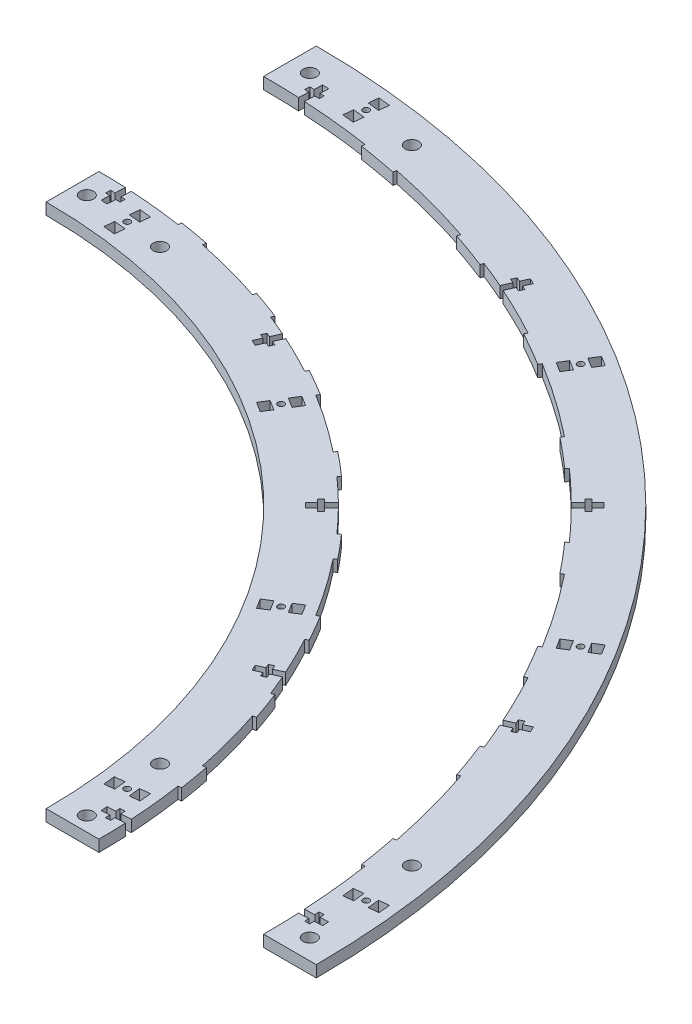
SolidWorks part; units mm, degrees
material "Custom Plastic"
ref_plane "Front Plane" through (0, 0, 0) normal (0, 0, 1) x (1, 0, 0)
ref_plane "Top Plane" through (0, 0, 0) normal (0, 1, 0) x (1, 0, 0)
ref_plane "Right Plane" through (0, 0, 0) normal (1, 0, 0) x (0, 0, -1)
sketch "Sketch1" plane through (0, 0, 0) normal (0, 1, 0) x (1, 0, 0)
  line L0 (280.2099, 0) -> (318.3099, 0)
  line L1 (318.3099, 0) -> (356.4099, 0)
  circle A0 centre (0, 0) radius 318.3099
  circle A1 centre (0, 0) radius 280.2099
  circle A2 centre (0, 0) radius 356.4099
  dimension "D1" = 636.6198
  dimension "D2" = 76.2
sketch "Sketch2" plane through (0, 0, 0) normal (0, 1, 0) x (1, 0, 0)
  line L0 (356.4099, 0) -> (383.3974, 0) construction
  line L1 (280.2099, 0) -> (253.2224, 0) construction
  line L2 (0, 0) -> (0, 470.2302) construction
  line L3 (0, 383.3974) -> (0, 253.2224)
  line L4 (383.3974, 0) -> (253.2224, 0)
  arc A0 (253.2224, 0) -> (0, 253.2224) centre (0, 0) ccw
  arc A1 (383.3974, 0) -> (0, 383.3974) centre (0, 0) ccw
  circle A3 centre (0, 0) radius 253.2224 construction
  circle A4 centre (0, 0) radius 383.3974 construction
  dimension "D1" = 26.9875
  dimension "D2" = 90
extrude "Boss-Extrude1" add sketch "Sketch2" along normal blind 5.588
sketch "Sketch6" plane through (0, 0, 0) normal (0, 1, 0) x (1, 0, 0)
  line L1 (318.3099, -318.3099) -> (-318.3099, -318.3099)
  line L2 (318.3099, -318.3099) -> (318.3099, 318.3099)
  line L3 (318.3099, 318.3099) -> (-318.3099, 318.3099)
  line L4 (-318.3099, -318.3099) -> (-318.3099, 318.3099)
  line L5 (318.3099, -318.3099) -> (-318.3099, 318.3099) construction
  line L6 (318.3099, 318.3099) -> (-318.3099, -318.3099) construction
  circle A0 centre (0, 0) radius 318.3099 construction
  point P0 (0, 0)
sketch "Sketch3" plane through (0, 0, 0) normal (0, 1, 0) x (1, 0, 0)
  line L0 (0, 0) -> (394.3747, 10.3271) construction
  line L1 (318.3099, 0) -> (356.4099, 0) construction
  line L2 (277.132, 41.4177) -> (275.562, 41.183)
  line L3 (0, 0) -> (390.1765, 58.3123) construction
  line L7 (354.0651, 52.9154) -> (352.495, 52.6807)
  line L8 (357.8747, 9.3713) -> (356.2878, 9.3297)
  line L10 (280.1139, 7.335) -> (278.5269, 7.2935)
  arc A1 (356.2878, 9.3297) -> (352.495, 52.6807) centre (0, 0) ccw
  circle A2 centre (0, 0) radius 356.4099 construction
  arc A4 (357.8747, 9.3713) -> (354.0651, 52.9154) centre (0, 0) ccw
  arc A6 (278.5269, 7.2935) -> (275.562, 41.183) centre (0, 0) ccw
  arc A7 (280.1139, 7.335) -> (277.132, 41.4177) centre (0, 0) ccw
  circle A8 centre (0, 0) radius 280.2099 construction
  dimension "D1" = 1.5
  dimension "D2" = 7
  dimension "D4" = 1.5875
extrude "Cut-Extrude2" cut sketch "Sketch3" along normal through all
sketch "Rotation Axis" plane through (0, 0, 0) normal (0, 0, 1) x (1, 0, 0)
  line L0 (0, 0) -> (0, 52.4129)
pattern_circular "CirPattern1" count 36 over 360 about axis through (0, 0, 0) along (0, 1, 0) of "Cut-Extrude2"
sketch "Sketch8" plane through (0, 0, 0) normal (0, 1, 0) x (1, 0, 0)
  line L0 (0, 0) -> (216.6823, 22.7742) construction
  line L1 (253.2224, 0) -> (383.3974, 0) construction
  line L2 (256.8637, 24.1881) -> (261.6001, 24.6859)
  line L3 (256.8637, 24.1881) -> (256.2796, 29.7455)
  line L4 (261.6001, 24.6859) -> (261.016, 30.2433)
  line L5 (256.2796, 29.7455) -> (261.016, 30.2433)
  line L6 (256.8637, 24.1881) -> (261.016, 30.2433) construction
  line L7 (261.6001, 24.6859) -> (256.2796, 29.7455) construction
  line L8 (361.0647, 35.14) -> (365.8011, 35.6379)
  line L9 (361.0647, 35.14) -> (360.4806, 40.6974)
  line L10 (365.8011, 35.6379) -> (365.217, 41.1952)
  line L11 (360.4806, 40.6974) -> (365.217, 41.1952)
  line L12 (361.0647, 35.14) -> (365.217, 41.1952) construction
  line L13 (365.8011, 35.6379) -> (360.4806, 40.6974) construction
  line L14 (267.9153, 25.3496) -> (272.6517, 25.8475)
  line L15 (267.9153, 25.3496) -> (267.3312, 30.907)
  line L16 (272.6517, 25.8475) -> (272.0676, 31.4048)
  line L17 (267.3312, 30.907) -> (272.0676, 31.4048)
  line L18 (267.9153, 25.3496) -> (272.0676, 31.4048) construction
  line L19 (272.6517, 25.8475) -> (267.3312, 30.907) construction
  line L20 (372.1163, 36.3016) -> (376.8527, 36.7994)
  line L21 (372.1163, 36.3016) -> (371.5322, 41.859)
  line L22 (376.8527, 36.7994) -> (376.2686, 42.3568)
  line L23 (371.5322, 41.859) -> (376.2686, 42.3568)
  line L24 (372.1163, 36.3016) -> (376.2686, 42.3568) construction
  line L25 (376.8527, 36.7994) -> (371.5322, 41.859) construction
  line L26 (261.308, 27.4646) -> (267.6232, 28.1283) construction
  line L27 (365.5091, 38.4166) -> (371.8243, 39.0803) construction
  circle A0 centre (264.4656, 27.7965) radius 1.524
  circle A1 centre (368.6667, 38.7484) radius 1.524
  arc A2 (383.3974, 0) -> (0, 383.3974) centre (0, 0) ccw construction
  arc A3 (253.2224, 0) -> (0, 253.2224) centre (0, 0) ccw construction
  point P5 (269.9914, 28.3772)
  point P6 (258.9398, 27.2157)
  point P7 (363.1409, 38.1676)
  point P13 (374.1925, 39.3292)
  point P29 (251.8352, 26.4689)
  point P30 (381.2971, 40.0759)
  dimension "D7" = 3.048
  dimension "D1" = 6
  dimension "D2" = 4.7625
  dimension "D3" = 5.588
  dimension "D4" = 6.35
  dimension "D5" = 4.7625
  dimension "D6" = 4.7625
extrude "Cut-Extrude3" cut sketch "Sketch8" along normal through all
pattern_circular "CirPattern3" count 4 every 26 about axis through (0, 0, 0) along (0, 1, 0) of "Cut-Extrude3"
sketch "Sketch11" plane through (0, 0, 0) normal (0, 1, 0) x (1, 0, 0)
  circle A0 centre (0, 0) radius 356.4099
  circle A1 centre (0, 0) radius 356.4099 construction
  circle A2 centre (0, 0) radius 280.2099
  circle A3 centre (0, 0) radius 280.2099 construction
extrude "Cut-Extrude7" cut sketch "Sketch11" along normal through all
sketch "Sketch12" plane through (0, 0, 0) normal (0, 1, 0) x (1, 0, 0)
  line L0 (0, 0) -> (536.846, 28.1349) construction
  line L1 (362.4514, 15.3241) -> (364.8293, 15.4487)
  line L2 (362.4514, 15.3241) -> (362.0676, 22.6464) construction
  line L3 (364.8293, 15.4487) -> (364.4456, 22.771) construction
  line L4 (362.0676, 22.6464) -> (364.4456, 22.771)
  line L5 (362.4514, 15.3241) -> (364.4456, 22.771) construction
  line L6 (364.8293, 15.4487) -> (362.0676, 22.6464) construction
  line L7 (355.9979, 17.131) -> (368.6805, 17.7956) construction
  line L8 (355.9979, 17.131) -> (355.8384, 20.1748)
  line L9 (368.6805, 17.7956) -> (368.521, 20.8395)
  line L10 (355.8384, 20.1748) -> (368.521, 20.8395) construction
  line L11 (355.9979, 17.131) -> (368.521, 20.8395) construction
  line L12 (368.6805, 17.7956) -> (355.8384, 20.1748) construction
  line L13 (271.2943, 10.5467) -> (273.6723, 10.6714)
  line L14 (271.2943, 10.5467) -> (270.9106, 17.869) construction
  line L15 (273.6723, 10.6714) -> (273.2886, 17.9937) construction
  line L16 (270.9106, 17.869) -> (273.2886, 17.9937)
  line L17 (271.2943, 10.5467) -> (273.2886, 17.9937) construction
  line L18 (273.6723, 10.6714) -> (270.9106, 17.869) construction
  line L19 (267.2189, 12.4783) -> (279.9015, 13.1429) construction
  line L20 (267.2189, 12.4783) -> (267.0594, 15.5221)
  line L21 (279.9015, 13.1429) -> (279.742, 16.1867)
  line L22 (267.0594, 15.5221) -> (279.742, 16.1867) construction
  line L23 (267.2189, 12.4783) -> (279.742, 16.1867) construction
  line L24 (279.9015, 13.1429) -> (267.0594, 15.5221) construction
  line L25 (280.2099, 0) -> (318.3099, 0) construction
  line L26 (267.0594, 15.5221) -> (271.0227, 15.7298)
  line L27 (271.0227, 15.7298) -> (270.9106, 17.869)
  line L28 (273.2886, 17.9937) -> (273.4007, 15.8544)
  line L29 (273.4007, 15.8544) -> (279.742, 16.1867)
  line L30 (273.6723, 10.6714) -> (273.5602, 12.8106)
  line L31 (273.5602, 12.8106) -> (279.9015, 13.1429)
  line L32 (271.2943, 10.5467) -> (271.1822, 12.686)
  line L33 (271.1822, 12.686) -> (267.2189, 12.4783)
  line L34 (362.0676, 22.6464) -> (362.1797, 20.5071)
  line L35 (362.1797, 20.5071) -> (355.8384, 20.1748)
  line L36 (364.4456, 22.771) -> (364.5577, 20.6318)
  line L37 (364.5577, 20.6318) -> (368.521, 20.8395)
  line L38 (368.6805, 17.7956) -> (364.7172, 17.5879)
  line L39 (364.7172, 17.5879) -> (364.8293, 15.4487)
  line L40 (362.4514, 15.3241) -> (362.3392, 17.4633)
  line L41 (362.3392, 17.4633) -> (355.9979, 17.131)
  line L58 (15.4071, 364.0367) -> (22.7294, 363.6529) construction
  circle A2 centre (0, 0) radius 280.2099 construction
  circle A3 centre (0, 0) radius 356.4099 construction
  point P4 (363.4485, 19.0475)
  point P5 (273.4804, 14.3325)
  point P6 (362.2595, 18.9852)
  point P12 (355.9182, 18.6529)
  point P18 (272.2914, 14.2702)
  dimension "D1" = 2.3813
  dimension "D2" = 7.3323
  dimension "D3" = 3.048
  dimension "D4" = 12.7
  dimension "D5" = 6.35
  dimension "D6" = 6.35
  dimension "D7" = 3
extrude "Cut-Extrude16" cut sketch "Sketch12" along normal blind 10 contours L41 L8 L35 L34 L4 L36 L37 L9 L38 L39 L1 L40
extrude "Cut-Extrude17" cut sketch "Sketch12<6>" along normal blind 10 contours L31 L21 L29 L28 L16 L27 L26 L20 L33 L32 L13 L30
sketch "Sketch12<6>" plane through (0, 0, 0) normal (0, 1, 0) x (1, 0, 0) same geometry as "Sketch12"
pattern_circular "CirPattern9" count 5 over 84 about axis through (0, 0, 0) along (0, 1, 0) of "Cut-Extrude16"
pattern_circular "CirPattern11" count 5 over 84 about axis through (0, 0, 0) along (0, 1, 0) of "Cut-Extrude17"
sketch "Sketch13" plane through (0, 0, 0) normal (0, 1, 0) x (1, 0, 0)
  line L0 (253.2224, 0) -> (280.2099, 0) construction
  line L1 (278.5269, 7.2935) -> (280.1139, 7.335)
  line L2 (280.2099, 0) -> (278.6224, 0)
  line L6 (356.4099, 0) -> (383.3974, 0) construction
  line L8 (357.8747, 9.3713) -> (356.2878, 9.3297)
  line L9 (357.9974, 0) -> (356.4099, 0)
  line L10 (0, 0) -> (128.7101, 128.7101) construction
  line L11 (0, 357.9974) -> (0, 356.4099)
  line L12 (9.3713, 357.8747) -> (9.3297, 356.2878)
  line L13 (0, 280.2099) -> (0, 278.6224)
  line L14 (7.2935, 278.5269) -> (7.335, 280.1139)
  arc A1 (278.6224, 0) -> (278.5269, 7.2935) centre (0, 0) ccw
  arc A2 (278.5269, 7.2935) -> (278.3161, 13.0598) centre (0, 0) ccw construction
  arc A3 (280.2099, 0) -> (280.1139, 7.335) centre (0, 0) ccw
  arc A7 (357.9974, 0) -> (357.8747, 9.3713) centre (0, 0) ccw
  arc A8 (356.4099, 0) -> (356.2878, 9.3297) centre (0, 0) ccw
  arc A9 (357.8747, 9.3713) -> (357.5833, 17.2141) centre (0, 0) ccw construction
  arc A10 (0, 356.4099) -> (9.3297, 356.2878) centre (0, 0) cw
  arc A11 (0, 357.9974) -> (9.3713, 357.8747) centre (0, 0) cw
  arc A12 (0, 280.2099) -> (7.335, 280.1139) centre (0, 0) cw
  arc A13 (0, 278.6224) -> (7.2935, 278.5269) centre (0, 0) cw
extrude "Cut-Extrude14" cut sketch "Sketch13" along normal through all
sketch "Sketch14" plane through (0, 0, 0) normal (0, 1, 0) x (1, 0, 0)
  line L0 (0, 0) -> (524.0996, 13.724) construction
  line L1 (0, 0) -> (454.2225, 80.0917) construction
  line L2 (318.3099, 0) -> (356.4099, 0) construction
  line L3 (280.2099, 0) -> (318.3099, 0) construction
  line L4 (0, 0) -> (56.2413, 56.2413) construction
  circle A0 centre (0, 0) radius 265.9224 construction
  circle A1 centre (0, 0) radius 370.6974 construction
  arc A2 (253.2224, 0) -> (0, 253.2224) centre (0, 0) ccw construction
  circle A3 centre (265.8313, 6.961) radius 3.2639
  circle A4 centre (0, 0) radius 356.4099 construction
  circle A5 centre (370.5704, 9.7037) radius 3.2639
  circle A6 centre (365.0657, 64.3709) radius 3.2639
  circle A7 centre (261.8824, 46.1769) radius 3.2639
  circle A8 centre (46.1769, 261.8824) radius 3.2639
  circle A9 centre (64.3709, 365.0657) radius 3.2639
  circle A10 centre (9.7037, 370.5704) radius 3.2639
  circle A11 centre (6.961, 265.8313) radius 3.2639
  dimension "D1" = 12.7
  dimension "D2" = 14.2875
  dimension "D3" = 6.5278
  dimension "D4" = 1.5
  dimension "D5" = 10
  dimension "D6" = 45
extrude "Cut-Extrude18" cut sketch "Sketch14" along normal through all
equation "\"TrackDiameter\"= \"TrackLength\" / pi"
equation "\"D1@Sketch1\"=\"TrackDiameter\""
equation "\"TrackLength\"= 2000"
equation "\"CorridorWidth\"=76.2"
equation "\"D2@Sketch1\"=\"CorridorWidth\""
